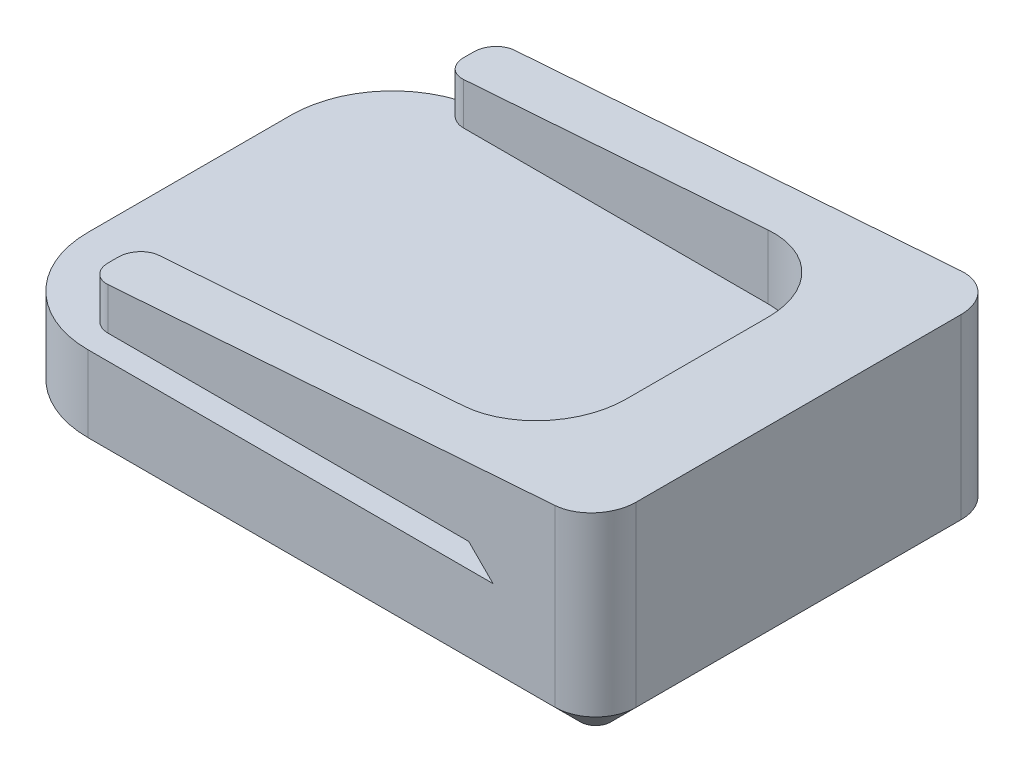
SolidWorks part; units mm, degrees
ref_plane "Front Plane" through (0, 0, 0) normal (0, 0, 1) x (1, 0, 0)
ref_plane "Top Plane" through (0, 0, 0) normal (0, 1, 0) x (1, 0, 0)
ref_plane "Right Plane" through (0, 0, 0) normal (1, 0, 0) x (0, 0, -1)
sketch "Sketch1" plane through (0, 0, 0) normal (0, 1, 0) x (1, 0, 0)
  line L1 (-12.7, -12.7) -> (16.51, -12.7)
  line L2 (-19.05, -6.35) -> (-19.05, 6.35)
  line L3 (-12.7, 12.7) -> (16.51, 12.7)
  line L4 (19.05, -10.16) -> (19.05, 10.16)
  line L5 (-19.05, -12.7) -> (19.05, 12.7) construction
  line L6 (-19.05, 12.7) -> (19.05, -12.7) construction
  arc A0 (-12.7, -12.7) -> (-19.05, -6.35) centre (-12.7, -6.35) cw
  arc A1 (-19.05, 6.35) -> (-12.7, 12.7) centre (-12.7, 6.35) cw
  arc A2 (16.51, -12.7) -> (19.05, -10.16) centre (16.51, -10.16) ccw
  arc A3 (16.51, 12.7) -> (19.05, 10.16) centre (16.51, 10.16) cw
  point P0 (0, 0)
  dimension "D3" = 6.35
  dimension "D4" = 2.54
  dimension "D1" = 25.4
  dimension "D2" = 38.1
extrude "Boss-Extrude1" add sketch "Sketch1" along normal blind 12.7
sketch "Sketch2" plane through (-19.05, 0, 0) normal (-1, 0, 0) x (0, 0, 1)
  line L0 (-12.7, 6.35) -> (12.7, 6.35) construction
  line L1 (-12.7, 12.7) -> (-12.7, 0) construction
  line L2 (12.7, 12.7) -> (12.7, 0) construction
  line L3 (0, 12.7) -> (0, 0) construction
  line L5 (-9.525, 6.35) -> (-9.525, 12.7)
  line L12 (-9.525, 6.35) -> (9.525, 6.35)
  line L15 (-9.525, 12.7) -> (9.525, 12.7)
  line L16 (12.7, 12.7) -> (6.35, 12.7) construction
  line L17 (9.525, 12.7) -> (9.525, 6.35)
  point P16 (0, 6.35)
  dimension "D2" = 19.05
  dimension "D1" = 19.05
extrude "Cut-Extrude1" cut sketch "Sketch2" against normal blind 31.75
sketch "Sketch3" plane through (0, 0, 12.7) normal (0, 0, 1) x (1, 0, 0)
  line L0 (19.05, 12.7) -> (-19.05, 12.7)
  line L1 (-19.05, 6.35) -> (19.05, 6.35) construction
  line L2 (19.05, 12.7) -> (19.05, 0) construction
  line L3 (-19.05, 12.7) -> (-19.05, 6.35)
  line L4 (-12.7, 10.414) -> (19.05, 12.7)
  line L6 (12.7, 7.239) -> (12.7, 7.874)
  line L7 (12.7, 7.874) -> (12.065, 7.874)
  line L10 (12.7, 6.985) -> (12.7, 7.239)
  line L11 (12.065, 7.874) -> (-12.7, 7.874)
  line L12 (-12.7, 7.874) -> (-12.7, 10.414)
  line L17 (-19.05, 6.35) -> (12.065, 6.35)
  line L18 (12.065, 6.35) -> (12.7, 6.35)
  line L19 (12.7, 6.35) -> (12.7, 6.985)
  point P8 (12.7, 6.35)
  point P12 (12.7, 7.874)
  point P13 (0, 0)
  point P15 (0, 0)
  dimension "D1" = 31.75
  dimension "D2" = 6.35
  dimension "D3" = 1.524
  dimension "D4" = 2.286
extrude "Cut-Extrude2" cut sketch "Sketch3" against normal through all
chamfer "Chamfer3" distance 1.5875 angle 45 10 edges at (1.905, 0, 12.7) (18.3061, 0, 11.9561) (19.05, 0, 0) (18.3061, 0, -11.9561) (1.905, 0, -12.7) (-17.1901, 0, -10.8401) (-17.1901, 0, 10.8401) (-19.05, 0, 0) (12.7, 7.874, 11.1125) (12.7, 7.874, -11.1125)
fillet "Fillet1" radius 1.27 4 edges at (-12.7, 9.144, 12.7) (-12.7, 9.144, 9.525) (-12.7, 9.144, -9.525) (-12.7, 9.144, -12.7)
fillet "Fillet2" radius 5.08 2 edges at (12.7, 9.2964, -9.525) (12.7, 9.2964, 9.525)
